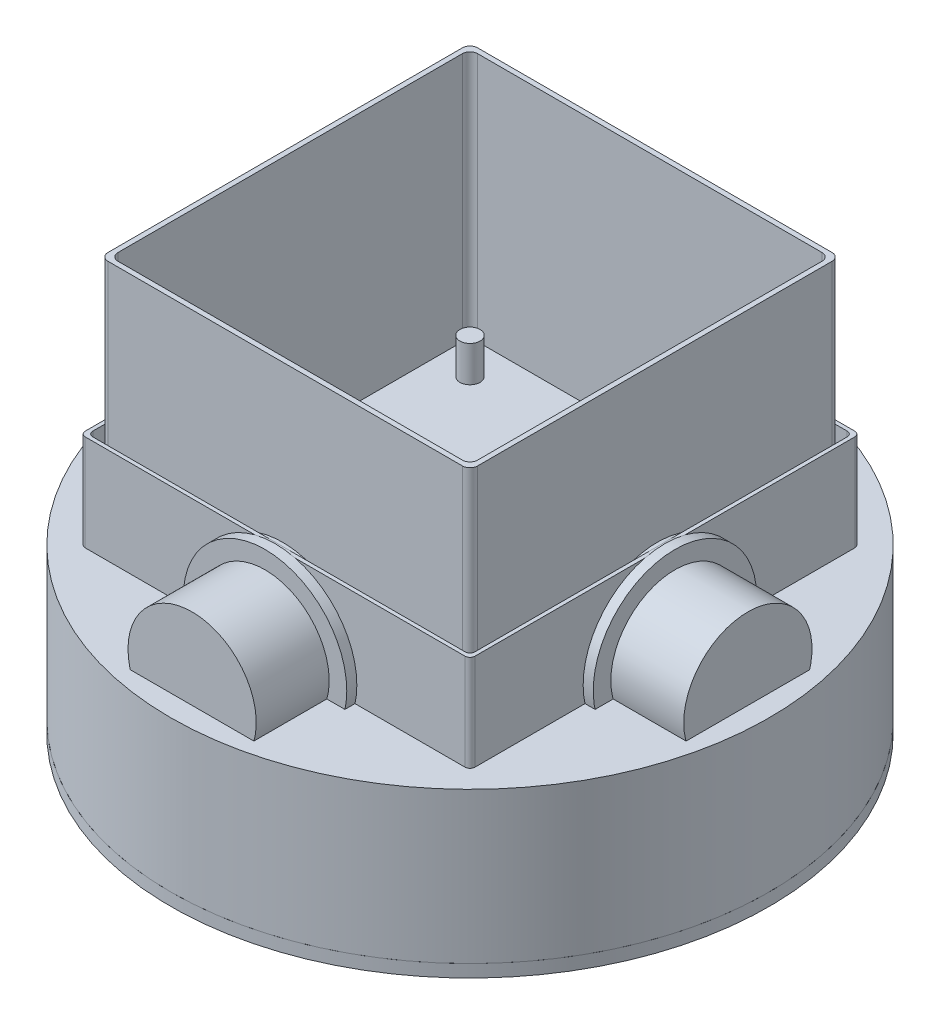
SolidWorks part; units mm, degrees
ref_plane "Спереди" through (0, 0, 0) normal (0, 0, 1) x (1, 0, 0)
ref_plane "Сверху" through (0, 0, 0) normal (0, 1, 0) x (1, 0, 0)
ref_plane "Справа" through (0, 0, 0) normal (1, 0, 0) x (0, 0, -1)
sketch "Эскиз1" plane through (0, 0, 0) normal (0, 0, 1) x (1, 0, 0)
  line L0 (0, 0) -> (119, 0)
  line L1 (119, 0) -> (119, 5)
  line L2 (119, 5) -> (107, 5)
  line L3 (107, 5) -> (103, 10)
  line L4 (103, 10) -> (0, 10)
  line L5 (0, 0) -> (0, 10)
  line L6 (103, 10) -> (103, 13.03)
  line L7 (103, 13.03) -> (0, 13.03)
  line L8 (0, 13.03) -> (0, 10)
  line L9 (119, 0) -> (119, 5)
  dimension "D1" = 119
  dimension "D2" = 5
  dimension "D3" = 12
  dimension "D4" = 10
  dimension "D5" = 16
  dimension "D6" = 3.03
revolve "основание" add sketch "Эскиз1" angle 360 about L5 region at (56.2217, 4.8363, 0) region at (51.5, 11.515, 0)
sketch "Эскиз2" plane through (0, 13.03, 0) normal (0, 1, 0) x (1, 0, 0)
  line L0 (0, 0) -> (0, 140.3858) construction
  line L2 (-62, 62) -> (62, 62) construction
  line L3 (-62, 62) -> (-62, -62) construction
  line L4 (-62, -62) -> (62, -62) construction
  line L5 (62, 62) -> (62, -62) construction
  circle A0 centre (-58, 58) radius 1.5
  circle A1 centre (58, 58) radius 1.5
  circle A2 centre (58, -58) radius 1.5
  circle A3 centre (-58, -58) radius 1.5
  dimension "D5" = 3
  dimension "D6" = 3
  dimension "D7" = 3
  dimension "D8" = 3
  dimension "D1" = 124
  dimension "D2" = 124
  dimension "D3" = 62
  dimension "D4" = 62
  dimension "D9" = 4
  dimension "D10" = 4
  dimension "D11" = 4
  dimension "D12" = 4
  dimension "D13" = 4
  dimension "D14" = 4
  dimension "D15" = 4
  dimension "D16" = 4
ref_plane "Плоскость отсчета" through (0, 13.23, 0) normal (0, 1, 0) x (1, 0, 0)
sketch "Эскиз гайки" plane through (0, 13.23, 0) normal (0, 1, 0) x (1, 0, 0)
  line L0 (53.9, 62.1) -> (62.1, 62.1)
  line L1 (-62.1, 62.1) -> (-53.9, 62.1)
  line L2 (-62.1, 62.1) -> (-62.1, 53.9)
  line L3 (-62.1, 53.9) -> (-53.9, 53.9)
  line L4 (-53.9, 62.1) -> (-53.9, 53.9)
  line L5 (-62.1, 62.1) -> (-53.9, 53.9) construction
  line L6 (-62.1, 53.9) -> (-53.9, 62.1) construction
  line L7 (53.9, 62.1) -> (53.9, 53.9)
  line L8 (53.9, 53.9) -> (62.1, 53.9)
  line L9 (62.1, 62.1) -> (62.1, 53.9)
  line L10 (53.9, 62.1) -> (62.1, 53.9) construction
  line L11 (53.9, 53.9) -> (62.1, 62.1) construction
  line L12 (53.9, -53.9) -> (62.1, -53.9)
  line L13 (53.9, -53.9) -> (53.9, -62.1)
  line L14 (53.9, -62.1) -> (62.1, -62.1)
  line L15 (62.1, -53.9) -> (62.1, -62.1)
  line L16 (53.9, -53.9) -> (62.1, -62.1) construction
  line L17 (53.9, -62.1) -> (62.1, -53.9) construction
  line L18 (-62.1, -53.9) -> (-53.9, -53.9)
  line L19 (-62.1, -53.9) -> (-62.1, -62.1)
  line L20 (-62.1, -62.1) -> (-53.9, -62.1)
  line L21 (-53.9, -53.9) -> (-53.9, -62.1)
  line L22 (-62.1, -53.9) -> (-53.9, -62.1) construction
  line L23 (-62.1, -62.1) -> (-53.9, -53.9) construction
  point P0 (-58, 58)
  point P5 (58, 58)
  point P12 (58, -58)
  point P17 (-58, -58)
  dimension "D1" = 8.2
  dimension "D2" = 8.2
  dimension "D3" = 8.2
  dimension "D4" = 8.2
  dimension "D5" = 8.2
  dimension "D6" = 8.2
  dimension "D7" = 8.2
  dimension "D8" = 8.2
extrude "гайки" add sketch "Эскиз гайки" along normal blind 2 separate body
sketch "Эскиз джем2" plane through (0, 15.23, 0) normal (0, 1, 0) x (1, 0, 0)
  line L0 (-62, -62) -> (62, -62)
  line L1 (-62, -62) -> (-62, 62)
  line L2 (-62, 62) -> (62, 62)
  line L3 (62, -62) -> (62, 62)
  line L4 (-22, 42) -> (28, 42)
  line L5 (-22, 42) -> (-22, -14)
  line L6 (-22, -14) -> (28, -14)
  line L7 (28, 42) -> (28, -14)
  point P18 (-58, 58)
  dimension "D3" = 4
  dimension "D1" = 124
  dimension "D2" = 124
  dimension "D13" = 4
  dimension "D15" = 20
  dimension "D16" = 40
  dimension "D17" = 50
  dimension "D18" = 56
extrude "джем2" add sketch "Эскиз джем2" along normal blind 0.5 separate body
sketch "Эскиз столбики1" plane through (0, 15.73, 0) normal (0, 1, 0) x (1, 0, 0)
  circle A0 centre (-58, 58) radius 4
  circle A1 centre (58, 58) radius 4
  circle A2 centre (58, -58) radius 4
  circle A3 centre (-58, -58) radius 4
  dimension "D1" = 8
  dimension "D2" = 8
  dimension "D3" = 8
  dimension "D4" = 8
extrude "столбики1" add sketch "Эскиз столбики1" along normal blind 15.5 separate body
sketch "Эскиз кольцо1" plane through (0, 31.23, 0) normal (0, 1, 0) x (1, 0, 0)
  line L0 (-62, -62) -> (62, -62)
  line L1 (-62, -62) -> (-62, 62)
  line L2 (-62, 62) -> (62, 62)
  line L3 (62, -62) -> (62, 62)
  line L4 (-44, 44) -> (44, 44)
  line L5 (-44, 44) -> (-44, -44)
  line L6 (-44, -44) -> (44, -44)
  line L7 (44, 44) -> (44, -44)
  line L8 (-41.4819, 49.4032) -> (-11.2419, 49.4032)
  line L9 (-41.4819, 49.4032) -> (-41.4819, 47.4032)
  line L10 (-41.4819, 47.4032) -> (-11.2419, 47.4032)
  line L11 (-11.2419, 49.4032) -> (-11.2419, 47.4032)
  dimension "D5" = 2
  dimension "D6" = 30.24
  dimension "D1" = 18
  dimension "D2" = 18
  dimension "D3" = 18
  dimension "D4" = 18
extrude "кольцо1" add sketch "Эскиз кольцо1" along normal blind 0.5 separate body
sketch "Эскиз столбики2" plane through (0, 31.73, 0) normal (0, 1, 0) x (1, 0, 0)
  circle A0 centre (-58, 58) radius 4
  circle A1 centre (58, 58) radius 4
  circle A2 centre (58, -58) radius 4
  circle A3 centre (-58, -58) radius 4
  dimension "D1" = 8
  dimension "D2" = 8
  dimension "D3" = 8
  dimension "D4" = 8
  dimension "D5" = 116
  dimension "D6" = 116
  dimension "D7" = 116
  dimension "D8" = 116
extrude "столбики2" add sketch "Эскиз столбики2" along normal blind 15.5 separate body
sketch "Эскиз кольцо2" plane through (0, 47.23, 0) normal (0, 1, 0) x (1, 0, 0)
  line L0 (-62, -62) -> (62, -62)
  line L1 (-62, -62) -> (-62, 62)
  line L2 (-62, 62) -> (62, 62)
  line L3 (62, -62) -> (62, 62)
  line L4 (-44, 44) -> (44, 44)
  line L5 (-44, 44) -> (-44, -44)
  line L6 (-44, -44) -> (44, -44)
  line L7 (44, 44) -> (44, -44)
  line L8 (-41.436, 49.2534) -> (-11.196, 49.2534)
  line L9 (-41.436, 49.2534) -> (-41.436, 47.2534)
  line L10 (-41.436, 47.2534) -> (-11.196, 47.2534)
  line L11 (-11.196, 49.2534) -> (-11.196, 47.2534)
  line L12 (-62, 62) -> (62, 62) construction
  line L13 (-62, 62) -> (-62, -62) construction
  dimension "D1" = 18
  dimension "D2" = 18
  dimension "D3" = 18
  dimension "D4" = 18
  dimension "D5" = 2
  dimension "D6" = 30.24
extrude "кольцо2" add sketch "Эскиз кольцо2" along normal blind 0.5 separate body
sketch "Эскиз столбики3" plane through (0, 47.73, 0) normal (0, 1, 0) x (1, 0, 0)
  circle A0 centre (-58, 58) radius 4
  circle A1 centre (58, 58) radius 4
  circle A2 centre (58, -58) radius 4
  circle A3 centre (-58, -58) radius 4
  dimension "D1" = 8
  dimension "D2" = 8
  dimension "D3" = 8
  dimension "D4" = 8
  dimension "D5" = 116
  dimension "D6" = 116
  dimension "D7" = 116
  dimension "D8" = 116
extrude "столбики3" add sketch "Эскиз столбики3" along normal blind 15.5 separate body
sketch "Эскиз джем1" plane through (0, 63.23, 0) normal (0, 1, 0) x (1, 0, 0)
  line L0 (40, 67) -> (37, 62)
  line L1 (-62, -62) -> (62, -62)
  line L2 (-62, -62) -> (-62, 62)
  line L3 (-62, 62) -> (62, 62)
  line L4 (62, -62) -> (62, 62)
  line L5 (51, 62) -> (40, 62)
  line L6 (51, 62) -> (51, 67)
  line L7 (51, 67) -> (40, 67)
  line L8 (29, 62) -> (18, 62)
  line L9 (29, 62) -> (29, 67)
  line L10 (29, 67) -> (18, 67)
  line L11 (18, 62) -> (18, 67)
  line L12 (-21, 32) -> (29, 32)
  line L13 (-21, 32) -> (-21, -24)
  line L14 (-21, -24) -> (29, -24)
  line L15 (29, 32) -> (29, -24)
  circle A0 centre (58, 58) radius 1.5 construction
  circle A1 centre (58, -58) radius 1.5 construction
  circle A2 centre (-58, -58) radius 1.5 construction
  circle M1 centre (-58, 58) radius 4
  dimension "D8" = 3
  dimension "D11" = 3
  dimension "D14" = 3
  dimension "D17" = 124
  dimension "D1" = 11
  dimension "D2" = 5
  dimension "D3" = 11
  dimension "D4" = 14
  dimension "D5" = 8
  dimension "D6" = 5
  dimension "D7" = 11
  dimension "D9" = 4
  dimension "D10" = 4
  dimension "D12" = 4
  dimension "D13" = 4
  dimension "D15" = 4
  dimension "D16" = 4
  dimension "D18" = 124
  dimension "D20" = 50
  dimension "D21" = 56
  dimension "D22" = 41
  dimension "D23" = 30
extrude "джем1" add sketch "Эскиз джем1" along normal blind 0.5 separate body contours L1 L4 L3 L2 L12 L15 L14 L13 M1 | M1 | L3 L2 M1 | L11 L3 L9 L10 | L6 L7 L0 L3 region at (44.72, 63.23, -64.4) region at (38.5, 63.23, -60.2464) region at (23.5, 63.23, -64.5) region at (-61.1065, 63.23, -61.1065) region at (-58, 63.23, -58)
sketch "Эскиз столбики4" plane through (0, 63.73, 0) normal (0, 1, 0) x (1, 0, 0)
  circle A0 centre (-58, 58) radius 4
  circle A1 centre (58, 58) radius 4
  circle A2 centre (58, -58) radius 4
  circle A3 centre (-58, -58) radius 4
  dimension "D1" = 8
  dimension "D2" = 8
  dimension "D3" = 8
  dimension "D4" = 8
extrude "столбики4" add sketch "Эскиз столбики4" along normal blind 15.5 separate body
ref_plane "Плоскость для R1" through (0, 50.73, 0) normal (0, 1, 0) x (1, 0, 0)
sketch "Эски R1" plane through (0, 50.73, 0) normal (0, 1, 0) x (1, 0, 0)
  line L0 (64.4775, 20.855) -> (62.4775, 20.855)
  line L1 (64.4775, 34.6815) -> (62.4775, 34.6815)
  line L2 (64.4775, 34.6815) -> (64.4775, 22.1815)
  line L3 (64.4775, 22.1815) -> (62.4775, 22.1815)
  line L4 (62.4775, 34.6815) -> (62.4775, 22.1815)
  line L5 (64.4775, 20.855) -> (64.4775, 8.355)
  line L6 (64.4775, 8.355) -> (62.4775, 8.355)
  line L7 (62.4775, 20.855) -> (62.4775, 8.355)
  line L8 (64.1263, -24.5455) -> (62.1263, -24.5455)
  line L9 (64.1263, -24.5455) -> (64.1263, -37.0455)
  line L10 (64.1263, -37.0455) -> (62.1263, -37.0455)
  line L11 (62.1263, -24.5455) -> (62.1263, -37.0455)
  line L12 (66.2613, -24.5564) -> (64.2613, -24.5564)
  line L13 (66.2613, -24.5564) -> (66.2613, -37.0564)
  line L14 (66.2613, -37.0564) -> (64.2613, -37.0564)
  line L15 (64.2613, -24.5564) -> (64.2613, -37.0564)
  dimension "D1" = 2
  dimension "D2" = 12.5
  dimension "D3" = 12.5
  dimension "D4" = 12.5
  dimension "D5" = 12.5
extrude "R1" add sketch "Эски R1" along normal blind 7 separate body
sketch "Эскиз для плоскости R2" plane through (0, 0, 0) normal (0, 0, 1) x (1, 0, 0)
  line L0 (-71.4303, 33.1043) -> (69.0475, 40.4278) construction
  line L2 (-71.4303, 33.1043) -> (-71.4303, 53.3646) construction
ref_plane "Плоскость вспомогательная R2" through (0, 0, 0) normal (0, 0, 1) x (1, 0, 0)
ref_plane "Плоскость R2" through (-1.9147, 36.7283, 0) normal (0.0521, -0.9986, 0) x (0.9986, 0.0521, 0)
sketch "Эскиз R2" plane through (-1.9147, 36.7283, 0) normal (0.0521, -0.9986, 0) x (0.9986, 0.0521, 0)
  line L0 (-31.7376, 64.1791) -> (-19.2376, 64.1791)
  line L1 (-47.2376, 64.1791) -> (-34.7376, 64.1791)
  line L2 (-47.2376, 64.1791) -> (-47.2376, 62.1791)
  line L3 (-47.2376, 62.1791) -> (-34.7376, 62.1791)
  line L4 (-34.7376, 64.1791) -> (-34.7376, 62.1791)
  line L5 (-31.7376, 64.1791) -> (-31.7376, 62.1791)
  line L6 (-31.7376, 62.1791) -> (-19.2376, 62.1791)
  line L7 (-19.2376, 64.1791) -> (-19.2376, 62.1791)
  line L8 (-16.2376, 64.1791) -> (-3.7376, 64.1791)
  line L9 (-16.2376, 64.1791) -> (-16.2376, 62.1791)
  line L10 (-16.2376, 62.1791) -> (-3.7376, 62.1791)
  line L11 (-3.7376, 64.1791) -> (-3.7376, 62.1791)
  line L12 (-0.7376, 64.1791) -> (11.7624, 64.1791)
  line L13 (-0.7376, 64.1791) -> (-0.7376, 62.1791)
  line L14 (-0.7376, 62.1791) -> (11.7624, 62.1791)
  line L15 (11.7624, 64.1791) -> (11.7624, 62.1791)
  line L16 (14.7624, 64.1791) -> (27.2624, 64.1791)
  line L17 (14.7624, 64.1791) -> (14.7624, 62.1791)
  line L18 (14.7624, 62.1791) -> (27.2624, 62.1791)
  line L19 (27.2624, 64.1791) -> (27.2624, 62.1791)
  line L20 (30.2624, 64.1791) -> (42.7624, 64.1791)
  line L21 (30.2624, 64.1791) -> (30.2624, 62.1791)
  line L22 (30.2624, 62.1791) -> (42.7624, 62.1791)
  line L23 (42.7624, 64.1791) -> (42.7624, 62.1791)
  line L24 (-61.2376, -62) -> (-61.2376, 62) construction
  dimension "D1" = 2
  dimension "D2" = 12.5
  dimension "D3" = 2
  dimension "D4" = 12.5
  dimension "D5" = 2
  dimension "D6" = 12.5
  dimension "D7" = 2
  dimension "D8" = 12.5
  dimension "D9" = 2
  dimension "D10" = 12.5
  dimension "D11" = 2
  dimension "D12" = 12.5
  dimension "D13" = 3
  dimension "D14" = 14
  dimension "D15" = 3
  dimension "D16" = 3
  dimension "D17" = 3
  dimension "D18" = 3
extrude "R2" add sketch "Эскиз R2" against normal blind 7 separate body
ref_plane "Плоскость R3" through (0, 32.73, 0) normal (0, 1, 0) x (1, 0, 0)
sketch "Эскиз R3" plane through (0, 32.73, 0) normal (0, 1, 0) x (1, 0, 0)
  line L0 (62.4775, 34.6815) -> (62.4775, 22.1815) construction
  line L1 (64.4775, 34.6815) -> (62.4775, 34.6815) construction
  line L2 (64.4775, 22.1815) -> (64.4775, 34.6815) construction
  line L3 (62.4775, 22.1815) -> (64.4775, 22.1815) construction
  line L4 (62.4775, 20.855) -> (62.4775, 8.355) construction
  line L5 (64.4775, 8.355) -> (64.4775, 20.855) construction
  line L6 (62.4775, 8.355) -> (64.4775, 8.355) construction
  line L7 (64.4775, 20.855) -> (62.4775, 20.855) construction
  line L8 (62.1263, -24.5455) -> (62.1263, -37.0455) construction
  line L9 (64.1263, -24.5455) -> (62.1263, -24.5455) construction
  line L10 (64.1263, -37.0455) -> (64.1263, -24.5455) construction
  line L11 (64.2613, -24.5564) -> (64.2613, -37.0564) construction
  line L12 (66.2613, -24.5564) -> (64.2613, -24.5564) construction
  line L13 (66.2613, -37.0564) -> (66.2613, -24.5564) construction
  line L14 (62.1263, -37.0455) -> (64.1263, -37.0455) construction
  line L15 (64.2613, -37.0564) -> (66.2613, -37.0564) construction
  line L16 (62.4775, 34.6815) -> (62.4775, 22.1815)
  line L17 (64.4775, 34.6815) -> (62.4775, 34.6815)
  line L18 (64.4775, 22.1815) -> (64.4775, 34.6815)
  line L19 (62.4775, 22.1815) -> (64.4775, 22.1815)
  line L20 (62.4775, 20.855) -> (62.4775, 8.355)
  line L21 (64.4775, 8.355) -> (64.4775, 20.855)
  line L22 (62.4775, 8.355) -> (64.4775, 8.355)
  line L23 (64.4775, 20.855) -> (62.4775, 20.855)
  line L24 (62.1263, -24.5455) -> (62.1263, -37.0455)
  line L25 (64.1263, -24.5455) -> (62.1263, -24.5455)
  line L26 (64.1263, -37.0455) -> (64.1263, -24.5455)
  line L27 (64.2613, -24.5564) -> (64.2613, -37.0564)
  line L28 (66.2613, -24.5564) -> (64.2613, -24.5564)
  line L29 (66.2613, -37.0564) -> (66.2613, -24.5564)
  line L30 (62.1263, -37.0455) -> (64.1263, -37.0455)
  line L31 (64.2613, -37.0564) -> (66.2613, -37.0564)
  line L32 (66.3837, -24.5537) -> (66.3837, -37.0537)
  line L33 (68.3837, -24.5537) -> (66.3837, -24.5537)
  line L34 (68.3837, -37.0537) -> (68.3837, -24.5537)
  line L35 (66.3837, -37.0537) -> (68.3837, -37.0537)
extrude "R3" add sketch "Эскиз R3" along normal blind 7 separate body
ref_plane "Плоскость R4" through (0, 16.73, 0) normal (0, 1, 0) x (1, 0, 0)
sketch "Эскиз R4" plane through (0, 16.73, 0) normal (0, 1, 0) x (1, 0, 0)
  line L0 (62.3037, 34.0109) -> (64.3037, 34.0109)
  line L1 (62.2897, 48.3949) -> (64.2897, 48.3949)
  line L2 (62.2897, 48.3949) -> (62.2897, 35.8949)
  line L3 (62.2897, 35.8949) -> (64.2897, 35.8949)
  line L4 (64.2897, 48.3949) -> (64.2897, 35.8949)
  line L5 (62.3037, 34.0109) -> (62.3037, 21.5109)
  line L6 (62.3037, 21.5109) -> (64.3037, 21.5109)
  line L7 (64.3037, 34.0109) -> (64.3037, 21.5109)
  line L8 (62.3082, 18.936) -> (64.3082, 18.936)
  line L9 (62.3082, 18.936) -> (62.3082, 6.436)
  line L10 (62.3082, 6.436) -> (64.3082, 6.436)
  line L11 (64.3082, 18.936) -> (64.3082, 6.436)
  dimension "D1" = 2
  dimension "D2" = 12.5
  dimension "D3" = 2
  dimension "D4" = 12.5
  dimension "D5" = 2
  dimension "D6" = 12.5
extrude "R4" add sketch "Эскиз R4" along normal blind 7 separate body
ref_plane "Плоскость изолятора" through (0, 14.23, 0) normal (0, 1, 0) x (1, 0, 0)
sketch "Эскиз изолятор" plane through (0, 14.23, 0) normal (0, 1, 0) x (1, 0, 0)
  line L1 (-70.5, 73.5) -> (70.5, 73.5)
  line L2 (-73.5, 70.5) -> (-73.5, -70.5)
  line L3 (-70.5, -73.5) -> (70.5, -73.5)
  line L4 (73.5, 70.5) -> (73.5, -70.5)
  line L5 (-73.5, 73.5) -> (73.5, -73.5) construction
  line L6 (-73.5, -73.5) -> (73.5, 73.5) construction
  line L7 (-68.5, 71.5) -> (68.5, 71.5)
  line L8 (-71.5, 68.5) -> (-71.5, -68.5)
  line L9 (-68.5, -71.5) -> (68.5, -71.5)
  line L10 (71.5, 68.5) -> (71.5, -68.5)
  arc A0 (-73.5, -70.5) -> (-70.5, -73.5) centre (-70.5, -70.5) ccw
  arc A1 (-71.5, -68.5) -> (-68.5, -71.5) centre (-68.5, -68.5) ccw
  arc A2 (70.5, -73.5) -> (73.5, -70.5) centre (70.5, -70.5) ccw
  arc A3 (68.5, -71.5) -> (71.5, -68.5) centre (68.5, -68.5) ccw
  arc A4 (70.5, 73.5) -> (73.5, 70.5) centre (70.5, 70.5) cw
  arc A5 (68.5, 71.5) -> (71.5, 68.5) centre (68.5, 68.5) cw
  arc A6 (-70.5, 73.5) -> (-73.5, 70.5) centre (-70.5, 70.5) ccw
  arc A7 (-68.5, 71.5) -> (-71.5, 68.5) centre (-68.5, 68.5) ccw
  point P0 (0, 0)
  dimension "D7" = 3
  dimension "D1" = 147
  dimension "D2" = 147
  dimension "D3" = 2
  dimension "D4" = 2
  dimension "D5" = 2
  dimension "D6" = 2
extrude "изолятор" add sketch "Эскиз изолятор" along normal blind 150 separate body
ref_plane "Плоскость ФЭУ" through (0, 40.23, 0) normal (0, -1, 0) x (-1, 0, 0)
sketch "Эскиз ФЭУ" plane through (0, 40.23, 0) normal (0, -1, 0) x (-1, 0, 0)
  line L1 (75.5, -77.5) -> (-75.5, -77.5)
  line L2 (77.5, -75.5) -> (77.5, 75.5)
  line L3 (75.5, 77.5) -> (-75.5, 77.5)
  line L4 (-77.5, -75.5) -> (-77.5, 75.5)
  line L5 (77.5, -77.5) -> (-77.5, 77.5) construction
  line L6 (77.5, 77.5) -> (-77.5, -77.5) construction
  line L7 (74, 76) -> (-74, 76)
  line L8 (76, 74) -> (76, -74)
  line L9 (74, -76) -> (-74, -76)
  line L10 (-76, 74) -> (-76, -74)
  arc A0 (75.5, -77.5) -> (77.5, -75.5) centre (75.5, -75.5) ccw
  arc A1 (76, -74) -> (74, -76) centre (74, -74) cw
  arc A2 (-75.5, -77.5) -> (-77.5, -75.5) centre (-75.5, -75.5) cw
  arc A3 (-74, -76) -> (-76, -74) centre (-74, -74) cw
  arc A4 (-75.5, 77.5) -> (-77.5, 75.5) centre (-75.5, 75.5) ccw
  arc A5 (-74, 76) -> (-76, 74) centre (-74, 74) ccw
  arc A6 (77.5, 75.5) -> (75.5, 77.5) centre (75.5, 75.5) ccw
  arc A7 (74, 76) -> (76, 74) centre (74, 74) cw
  point P0 (0, 0)
  dimension "D7" = 2
  dimension "D1" = 155
  dimension "D2" = 155
  dimension "D3" = 1.5
  dimension "D4" = 1.5
  dimension "D5" = 1.5
  dimension "D6" = 1.5
extrude "каркас ФЭУ" add sketch "Эскиз ФЭУ" against normal blind 63 separate body
sketch "Эскиз отв1" plane through (0, 0, 77.5) normal (0, 0, 1) x (1, 0, 0)
  line L0 (0, 103.23) -> (0, 40.23) construction
  line L1 (75.5, 103.23) -> (-75.5, 103.23) construction
  line L2 (75.5, 40.23) -> (-75.5, 40.23) construction
  line L3 (0, 71.73) -> (32.4207, 71.73) construction
  circle A0 centre (0, 71.73) radius 25.5
  dimension "D1" = 51
extrude "Вырез-1" cut sketch "Эскиз отв1" against normal up to surface (155 mm away) up to face at (0, 71.73, -77.5)
sketch "Эскиз отв2" plane through (77.5, 0, 0) normal (1, 0, 0) x (0, 0, -1)
  line L0 (0, 103.23) -> (0, 40.23) construction
  line L1 (75.5, 103.23) -> (-75.5, 103.23) construction
  line L2 (75.5, 40.23) -> (-75.5, 40.23) construction
  line L3 (0, 71.73) -> (33.5772, 71.73) construction
  circle A0 centre (0, 71.73) radius 25.5
  dimension "D1" = 51
extrude "Вырез-2" cut sketch "Эскиз отв2" against normal up to surface (155 mm away) up to face at (-77.5, 71.73, 0)
sketch "Эскиз шайба1" plane through (0, 0, 76) normal (0, 0, -1) x (-1, 0, 0)
  circle A0 centre (0, 71.73) radius 25.5
  circle A1 centre (0, 71.73) radius 31.5
  dimension "D1" = 51
  dimension "D2" = 63
extrude "шайба1" add sketch "Эскиз шайба1" along normal blind 2.48
sketch "Эскиз шайба2" plane through (76, 0, 0) normal (-1, 0, 0) x (0, 0, 1)
  circle A0 centre (0, 71.73) radius 25.5
  circle A1 centre (0, 71.73) radius 31.5
  dimension "D1" = 51
  dimension "D2" = 63
extrude "шайба2" add sketch "Эскиз шайба2" along normal blind 2.48
sketch "Эскиз шайба3" plane through (0, 0, -76) normal (0, 0, 1) x (1, 0, 0)
  circle A0 centre (0, 71.73) radius 25.5
  circle A1 centre (0, 71.73) radius 31.5
  dimension "D1" = 51
  dimension "D2" = 63
extrude "шайба3" add sketch "Эскиз шайба3" along normal blind 2.48
sketch "Эскиз шайба4" plane through (-76, 0, 0) normal (1, 0, 0) x (0, 0, -1)
  circle A0 centre (0, 71.73) radius 25.5
  circle A1 centre (0, 71.73) radius 31.5
  dimension "D1" = 51
  dimension "D2" = 63
extrude "шайба4" add sketch "Эскиз шайба4" along normal blind 2.48
chamfer "Фаска для шайб" distance 1 angle 60 4 edges at (31.5, 71.73, -73.52) (73.52, 71.73, 31.5) (-73.52, 71.73, -31.5) (-31.5, 71.73, 73.52) first distance on face at (31.5, 71.73, -73.52) first distance on face at (73.52, 71.73, 31.5) first distance on face at (-73.52, 71.73, -31.5) first distance on face at (-31.5, 71.73, 73.52)
sketch "Эскиз ФЭУ_1_1" plane through (0, 0, 77.5) normal (0, 0, 1) x (1, 0, 0)
  circle A0 centre (0, 71.73) radius 32.5
  dimension "D1" = 65
sketch "Эскиз ФЭУ_1_2" plane through (77.5, 0, 0) normal (1, 0, 0) x (0, 0, -1)
  circle A0 centre (0, 71.73) radius 32.5
  dimension "D1" = 65
sketch "Эскиз ФЭУ_1_3" plane through (0, 0, -77.5) normal (0, 0, -1) x (-1, 0, 0)
  circle A0 centre (0, 71.73) radius 32.5
  dimension "D1" = 65
sketch "Эскиз ФЭУ_1_4" plane through (-77.5, 0, 0) normal (-1, 0, 0) x (0, 0, 1)
  circle A0 centre (0, 71.73) radius 32.5
  dimension "D1" = 65
extrude "Бобышка-ФЭУ_1_1" add sketch "Эскиз ФЭУ_1_1" along normal blind 4
extrude "Бобышка-ФЭУ_1_2" add sketch "Эскиз ФЭУ_1_2" along normal blind 4
extrude "Бобышка-ФЭУ_1_3" add sketch "Эскиз ФЭУ_1_3" along normal blind 4
extrude "Бобышка-ФЭУ_1_4" add sketch "Эскиз ФЭУ_1_4" along normal blind 4
sketch "Эскиз-ФЭУ_2_1" plane through (0, 0, 81.5) normal (0, 0, 1) x (1, 0, 0)
  line L0 (0, 103.23) -> (0, 40.23) construction
  circle A0 centre (0, 71.73) radius 25.5
  dimension "D1" = 51
sketch "Эскиз-ФЭУ_2_2" plane through (81.5, 0, 0) normal (1, 0, 0) x (0, 0, -1)
  circle A0 centre (0, 71.73) radius 25.5
  dimension "D1" = 51
sketch "Эскиз-ФЭУ_2_3" plane through (0, 0, -81.5) normal (0, 0, -1) x (-1, 0, 0)
  circle A0 centre (0, 71.73) radius 25.5
  dimension "D1" = 51
sketch "Эскиз-ФЭУ_2_4" plane through (-81.5, 0, 0) normal (-1, 0, 0) x (0, 0, 1)
  circle A0 centre (0, 71.73) radius 25.5
  dimension "D1" = 51
extrude "Бобышка-ФЭУ_2_1" add sketch "Эскиз-ФЭУ_2_1" along normal blind 29
extrude "Бобышка-ФЭУ_2_2" add sketch "Эскиз-ФЭУ_2_2" along normal blind 29
extrude "Бобышка-ФЭУ_2_3" add sketch "Эскиз-ФЭУ_2_3" along normal blind 29
extrude "Бобышка-ФЭУ_2_4" add sketch "Эскиз-ФЭУ_2_4" along normal blind 29
ref_plane "Плоскость для вращения ФЭУ" through (0, 71.73, 0) normal (0, -1, 0) x (-1, 0, 0)
sketch "Эскиз Аргон" plane through (0, 5, 0) normal (0, 1, 0) x (1, 0, 0)
  circle A0 centre (0, 0) radius 119
  dimension "D1" = 238
extrude "Жидкий Аргон" add sketch "Эскиз Аргон" along normal blind 60 separate body
equation "\"D3@Эскиз2\"=124/2"
equation "\"D4@Эскиз2\"=124/2"
equation "\"D15@Эскиз R2\"=\"D13@Эскиз R2\""
equation "\"D16@Эскиз R2\"=\"D13@Эскиз R2\""
equation "\"D17@Эскиз R2\"=\"D13@Эскиз R2\""
equation "\"D18@Эскиз R2\"=\"D13@Эскиз R2\""
